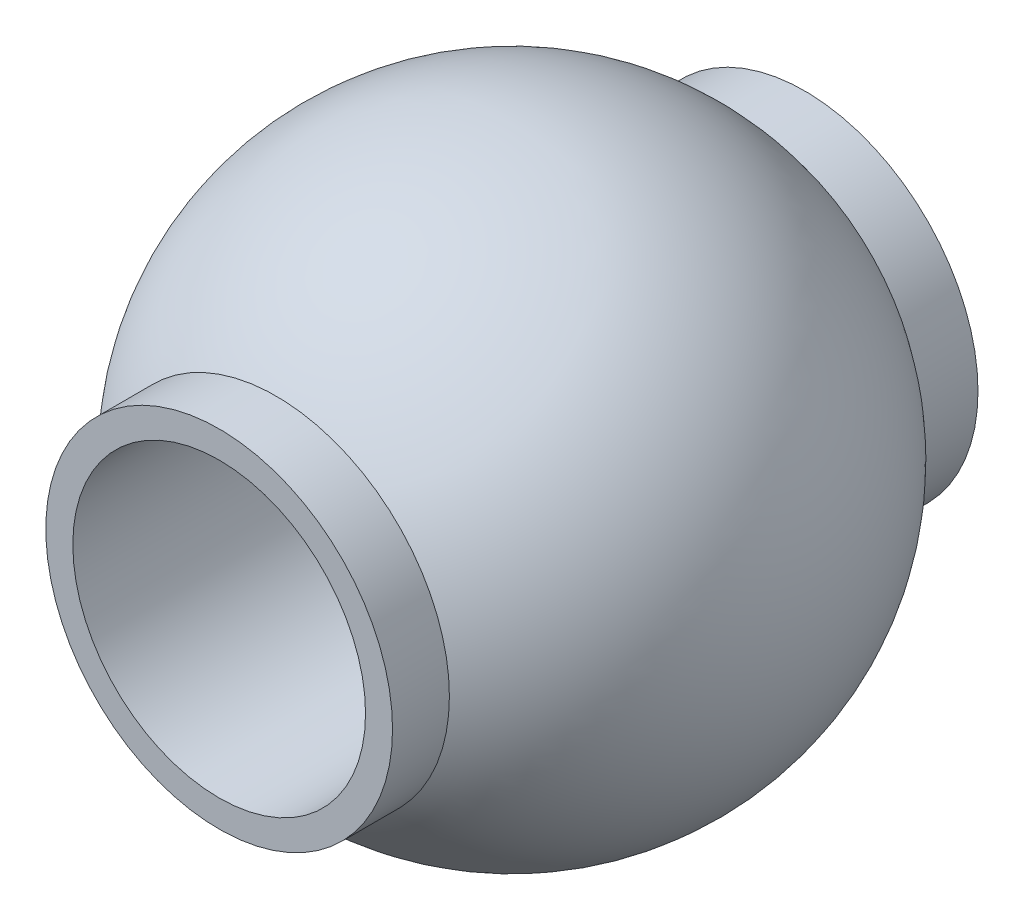
SolidWorks part; units mm, degrees
ref_plane "Plan de face" through (0, 0, 0) normal (0, 0, 1) x (1, 0, 0)
ref_plane "Plan de dessus" through (0, 0, 0) normal (0, 1, 0) x (1, 0, 0)
ref_plane "Plan de droite" through (0, 0, 0) normal (1, 0, 0) x (0, 0, -1)
sketch "Esquisse1" plane through (0, 0, 0) normal (0, 0, 1) x (1, 0, 0)
  line L0 (0, 4.208) -> (0, -5.9493) construction
  line L1 (0, -3) -> (0, 3)
  arc A0 (0, 3) -> (0, -3) centre (0, 0) ccw
  dimension "D1" = 6
revolve "Révolution1" add sketch "Esquisse1" angle 360 about L0
sketch "Esquisse2" plane through (0, 0, 0) normal (0, 0, 1) x (1, 0, 0)
  circle A0 centre (0, 0) radius 1.5
  dimension "D1" = 3
extrude "Enlèv. mat.-Extru.1" cut sketch "Esquisse2" against normal through all and the other way through all
sketch "Esquisse3" plane through (0, 0, 0) normal (0, 0, 1) x (1, 0, 0)
  circle A0 centre (0, 0) radius 1.5 construction
  circle A1 centre (0, 0) radius 1.5
  circle A2 centre (0, 0) radius 1.7767
extrude "Boss.-Extru.1" add sketch "Esquisse3" along normal blind 3 and the other way blind 3
